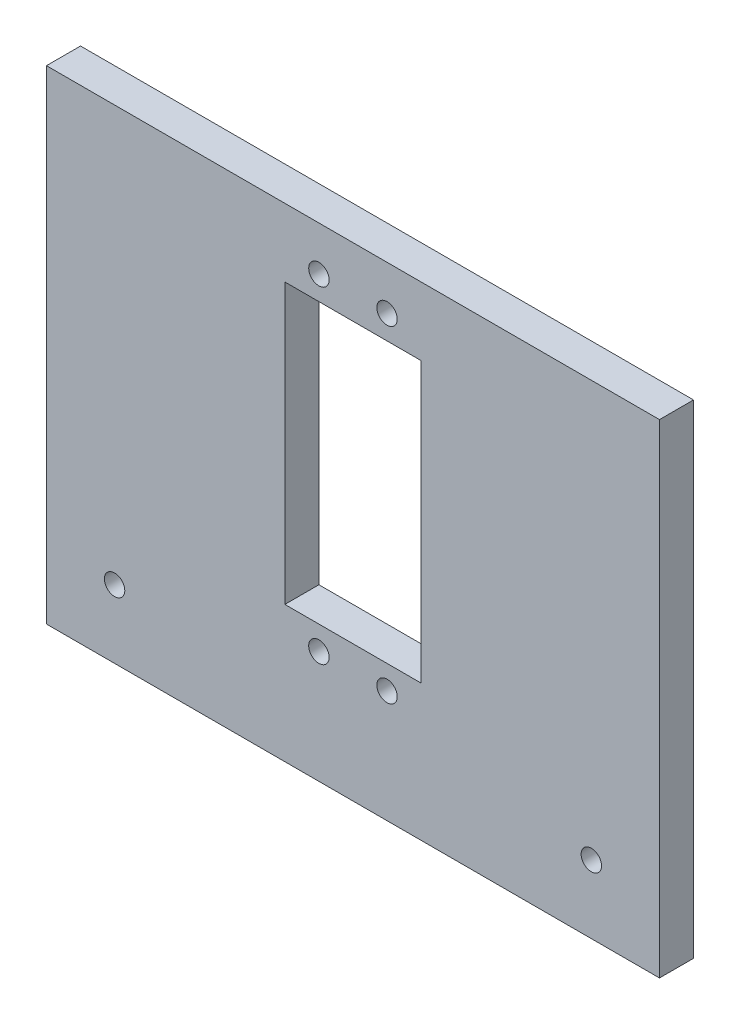
SolidWorks part; units mm, degrees
ref_plane "Plan de face" through (0, 0, 0) normal (0, 0, 1) x (1, 0, 0)
ref_plane "Plan de dessus" through (0, 0, 0) normal (0, 1, 0) x (1, 0, 0)
ref_plane "Plan de droite" through (0, 0, 0) normal (1, 0, 0) x (0, 0, -1)
sketch "Esquisse1" plane through (0, 0, 0) normal (0, 0, 1) x (1, 0, 0)
  line L0 (45, 71) -> (45, 0) construction
  line L1 (0, 0) -> (90, 0)
  line L2 (0, 0) -> (0, 71)
  line L3 (0, 71) -> (90, 71)
  line L4 (90, 0) -> (90, 71)
  line L5 (35, 40.5) -> (55, 40.5) construction
  line L6 (35, 61) -> (55, 61)
  line L7 (35, 61) -> (35, 20)
  line L8 (35, 20) -> (55, 20)
  line L9 (55, 61) -> (55, 20)
  circle A0 centre (40, 16.5) radius 1.5
  circle A1 centre (50, 16.5) radius 1.5
  circle A2 centre (50, 64.5) radius 1.5
  circle A3 centre (40, 64.5) radius 1.5
  circle A4 centre (10, 10) radius 1.5
  circle A5 centre (80, 10) radius 1.5
  dimension "D6" = 3.5
  dimension "D8" = 3
  dimension "D9" = 3
  dimension "D1" = 20
  dimension "D2" = 41
  dimension "D3" = 20
  dimension "D4" = 10
  dimension "D5" = 90
  dimension "D7" = 5
  dimension "D10" = 10
  dimension "D11" = 35
extrude "Boss.-Extru.1" add sketch "Esquisse1" along normal blind 5
